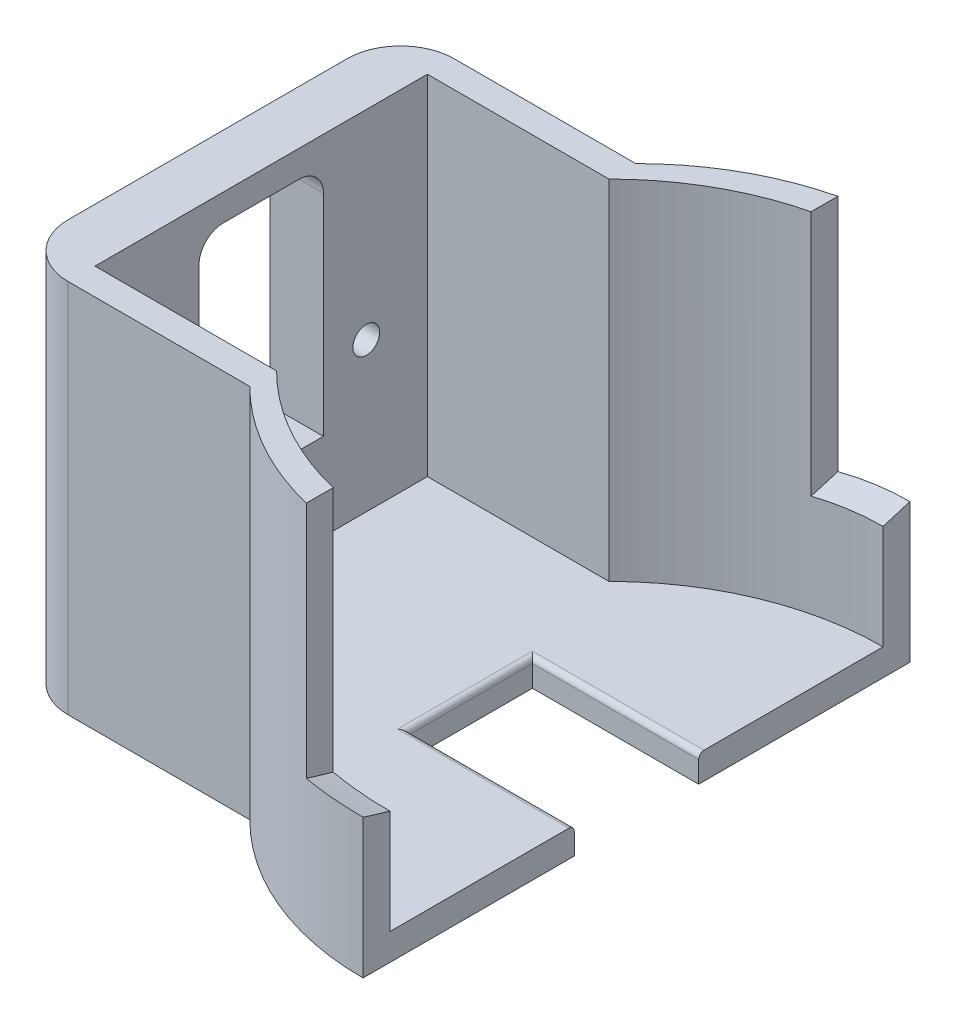
SolidWorks part; units mm, degrees
ref_plane "Plan de face" through (0, 0, 0) normal (0, 0, 1) x (1, 0, 0)
ref_plane "Plan de dessus" through (0, 0, 0) normal (0, 1, 0) x (1, 0, 0)
ref_plane "Plan de droite" through (0, 0, 0) normal (1, 0, 0) x (0, 0, -1)
sketch "Esquisse1" plane through (0, 0, 0) normal (0, 1, 0) x (1, 0, 0)
  line L0 (-50.0182, 0) -> (81.7007, 0) construction
  line L1 (0, 51) -> (0, 46)
  line L2 (-70, 31) -> (-36.1248, 31)
  line L3 (-70, 31) -> (-70, -31)
  line L4 (0, 46) -> (0, -46)
  line L5 (0, 68.3448) -> (0, -68.3448) construction
  line L6 (-36.1248, 36) -> (-80, 36)
  line L7 (-80, 36) -> (-80, -36)
  line L8 (-80, -36) -> (-36.1248, -36)
  line L9 (-70, -31) -> (-36.1248, -31)
  line L10 (0, -46) -> (0, -51)
  arc A0 (-36.1248, -36) -> (0, -51) centre (0, 0) ccw
  arc A1 (0, 51) -> (-36.1248, 36) centre (0, 0) ccw
  arc A2 (-36.1248, 31) -> (0, 46) centre (0, -5) cw
  arc A3 (-36.1248, -31) -> (0, -46) centre (0, 5) ccw
  point P14 (-50, 0)
  point P21 (-19.5576, 42.101)
  point P22 (-19.5576, 47.101)
  point P23 (-19.5576, -42.101)
  point P24 (-19.5576, -47.101)
  dimension "D6" = 102
  dimension "D1" = 5
  dimension "D2" = 72
  dimension "D3" = 80
  dimension "D4" = 10
  dimension "D5" = 5
  dimension "D7" = 5
  dimension "D8" = 5
extrude "Boss.-Extru.5" add sketch "Esquisse1" along normal mid plane 100 contours A3 L9 L3 L2 A2 L1 A1 L6 L7 L8 A0 L10 region at (-1.2963, 0, -48.5)
sketch "Esquisse5" plane through (-70, 0, 0) normal (1, 0, 0) x (0, 0, -1)
  line L1 (-11.6, -2) -> (11.6, -2)
  line L2 (-11.6, -2) -> (-11.6, -33.8)
  line L3 (-11.6, -33.8) -> (11.6, -33.8)
  line L4 (11.6, -2) -> (11.6, -33.8)
  line L5 (-11.6, -2) -> (-11.6, 5.5)
  line L6 (11.6, -2) -> (11.6, 5.5)
  line L7 (-7.1, 10) -> (7.1, 10)
  arc A0 (-11.6, 5.5) -> (-7.1, 10) centre (-7.1, 5.5) cw
  arc A1 (7.1, 10) -> (11.6, 5.5) centre (7.1, 5.5) cw
  circle A2 centre (0, 0) radius 2.15
  dimension "D3" = 4.3
  dimension "D6" = 4.5
  dimension "D7" = 4.5
  dimension "D1" = 2
  dimension "D2" = 11.6
  dimension "D4" = 43.8
  dimension "D5" = 23.2
  dimension "D8" = 12
extrude "Enlèv. mat.-Extru.1" cut sketch "Esquisse5" against normal blind 10 contours A2 L1 L6 A1 L7 A0 L5 | A2 L1 L2 L3 L4 | L1 A2 | L1 A2 region at (-70, 4.0537, 0) region at (-70, -17.9034, 0) region at (-70, 0.0228, 0) region at (-70, -2.0602, 0)
sketch "Esquisse8" plane through (0, -50, 0) normal (0, 1, 0) x (1, 0, 0)
  line L0 (0, -51) -> (0, 51)
  line L1 (-36.1248, -36) -> (-80, -36)
  line L2 (-80, -36) -> (-80, 36)
  line L3 (-80, 36) -> (-36.1248, 36)
  arc A0 (0, 51) -> (-36.1248, 36) centre (0, 0) ccw construction
  arc A1 (0, -51) -> (-36.1248, -36) centre (0, 0) cw
  arc A2 (-36.1248, -36) -> (0, -51) centre (0, 0) ccw construction
  arc A3 (-36.1248, 36) -> (0, 51) centre (0, 0) cw
extrude "Boss.-Extru.6" add sketch "Esquisse8" against normal blind 5
sketch "Esquisse9" plane through (0, 0, 0) normal (1, 0, 0) x (0, 0, -1)
  line L0 (-51, 50) -> (-51, -55) construction
  line L1 (-51, 15) -> (51, 15)
  line L2 (-51, 15) -> (-51, 50)
  line L3 (-51, 50) -> (51, 50)
  line L4 (51, 15) -> (51, 50)
  line L5 (-7.1, 10) -> (7.1, 10) construction
  dimension "D1" = 5
extrude "Enlèv. mat.-Extru.2" cut sketch "Esquisse9" against normal through all
sketch "Esquisse10" plane through (0, 0, 0) normal (1, 0, 0) x (0, 0, -1)
  line L0 (85.2632, 65.694) -> (136.2871, 33.4867)
  line L1 (0, 23.2055) -> (0, -37) construction
  line L2 (-136.2871, 33.4867) -> (-85.2632, 65.694)
  line L3 (85.2632, 65.694) -> (136.2871, 33.4867) construction
  arc A0 (-85.2632, 65.694) -> (85.2632, 65.694) centre (0, 130) ccw
  arc A1 (-136.2871, 33.4867) -> (136.2871, 33.4867) centre (0, 130) ccw
  arc A3 (-73.5134, 52.5348) -> (49.5522, 35.3974) centre (0, 130) ccw
  point P0 (0, 23.2055)
  line M2 (-46, 15) -> (-51, 15)
  line M3 (-51, 15) -> (-51, -55)
  line M5 (51, -55) -> (51, 15)
  line M6 (51, 15) -> (46, 15)
  line M7 (46, 15) -> (46, -50)
  line M9 (-46, -50) -> (-46, 15)
  dimension "D3" = 37
  dimension "D7" = 167
  dimension "D10" = 11.7498
sketch "Esquisse11" plane through (-70, 0, 0) normal (1, 0, 0) x (0, 0, -1)
  line L0 (0, 0) -> (0, -23.2285) construction
  line L1 (-11.6, -2) -> (-11.6, -33.8) construction
  line L3 (31, -50) -> (-31, -50) construction
  line L5 (12.6, -50) -> (46, -50) construction
  circle A0 centre (-19.6, -22.214) radius 2.5
  circle A1 centre (19.6, -22.214) radius 2.5
  circle A2 centre (0, 126.5) radius 150
  point P6 (0, -23.5)
  dimension "D1" = 300
  dimension "D3" = 5
  dimension "D2" = 23.5
  dimension "D4" = 8
  dimension "D5" = 39.2
  dimension "D6" = 27.786
extrude "Enlèv. mat.-Extru.9" cut sketch "Esquisse11" against normal blind 5 contours A0 | A1
extrude "Enlèv. mat.-Extru.12" cut sketch "Esquisse10" against normal blind 12 contours L2 A1 L0 A0 M3 M2 M9 M7 M6 M5 | A1 M3 M9 M2 | A1 M7 M5 M6 region at (0, 11.0584, 0) region at (0, -7.3997, -48.4859) region at (0, -7.3997, 48.4859)
fillet "Congé1" radius 10 2 edges at (-80, -20, 36) (-80, -20, -36)
sketch "Esquisse12" plane through (0, -55, 0) normal (0, -1, 0) x (-1, 0, 0)
  line L0 (5.4841, 0) -> (-5.4841, 0) construction
  line L8 (31, -11.6) -> (0, -11.6)
  line L9 (31, -11.6) -> (31, 11.6)
  line L10 (31, 11.6) -> (0, 11.6)
  line L11 (0, -11.6) -> (0, 11.6)
  line L12 (0, -51) -> (0, 51) construction
  dimension "D2" = 23.2
  dimension "D10" = 31
extrude "Enlèv. mat.-Extru.13" cut sketch "Esquisse12" against normal blind 10
fillet "Congé2" radius 1 3 edges at (-15.5, -50, -11.6) (-31, -50, 0) (-15.5, -50, 11.6)
